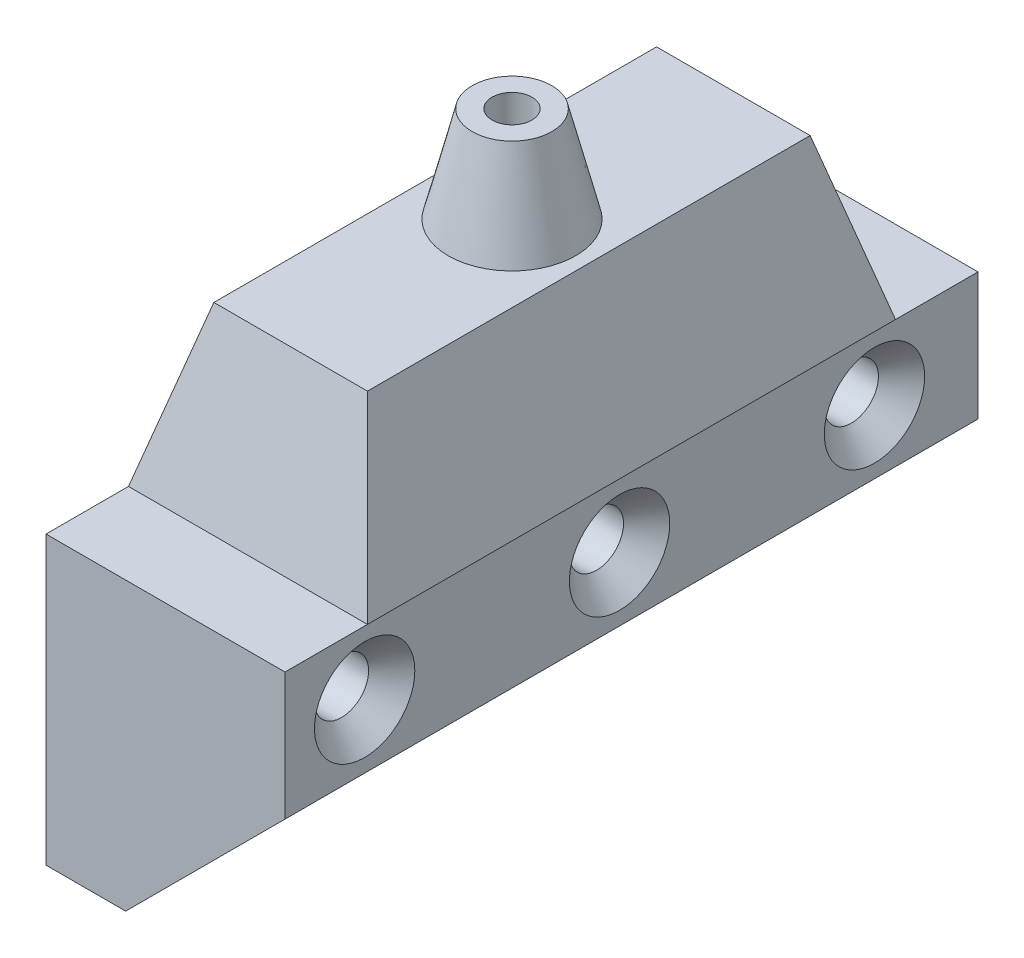
SolidWorks part; units mm, degrees
ref_plane "Plan de face" through (0, 0, 0) normal (0, 0, 1) x (1, 0, 0)
ref_plane "Plan de dessus" through (0, 0, 0) normal (0, 1, 0) x (1, 0, 0)
ref_plane "Plan de droite" through (0, 0, 0) normal (1, 0, 0) x (0, 0, -1)
sketch "Main-Sketch" plane through (0, 0, 0) normal (0, 0, 1) x (1, 0, 0)
  line L0 (0, 8) -> (2.6795, 18)
  line L1 (0, 0) -> (15, 0)
  line L2 (0, 0) -> (0, 8)
  line L3 (2.6795, 18) -> (12.3205, 18)
  line L4 (15, 0) -> (15, 8)
  line L5 (12.3205, 18) -> (15, 8)
  dimension "D1" = 15
  dimension "D2" = 8
  dimension "D3" = 165
  dimension "D4" = 10
extrude "Main-Extrusion" add sketch "Main-Sketch" along normal blind 43.5
ref_plane "Plan-Left" through (0, 11.4109, 42.5861) normal (0, 0.2588, 0.9659) x (-1, 0, 0)
ref_plane "Plan-Left2" through (0, 10.1168, 37.7564) normal (0, 0.2588, 0.9659) x (-1, 0, 0)
ref_axis "Axe-Left" through (2.6795, 18, 35.6441) along (1, 0, 0)
sketch "Left-Sketch" plane through (0, 10.1168, 37.7564) normal (0, 0.2588, 0.9659) x (-1, 0, 0)
  line L1 (0, 2.1915) -> (-15, 2.1915)
  line L2 (0, 2.1915) -> (0, -8.1613)
  line L3 (0, -8.1613) -> (-15, -8.1613)
  line L4 (-15, 2.1915) -> (-15, -8.1613)
  line L8 (0, 3.5312) -> (0, -7.7274) construction
  line L11 (-2.6795, -8.1613) -> (-12.3205, -8.1613) construction
  point P5 (0, 0)
  point P7 (0, 0)
  point P10 (-15, -11.5247)
  point P11 (0, 0)
  point P14 (-15, 3.0646)
  point P15 (-15, 0.4513)
extrude "Left-Hole" cut sketch "Left-Sketch" along normal through all
sketch "Esquisse8" plane through (15, 0, 0) normal (1, 0, 0) x (0, 0, -1)
  line L1 (-43.5, 8) -> (-38.3236, 8)
  line L2 (-43.5, 8) -> (-43.5, 13)
  line L3 (-43.5, 13) -> (-38.3236, 13)
  line L4 (-38.3236, 8) -> (-38.3236, 13)
  point P5 (-38.3236, 8)
  point P7 (-43.5, 9.3209)
  point P8 (-43.5, 10.368)
  dimension "D1" = 5
extrude "Left-Hole2" cut sketch "Esquisse8" against normal through all
ref_plane "Plan-Right" through (0, 0.5359, -2) normal (0, 0.2588, -0.9659) x (-1, 0, 0)
ref_plane "Plan-Right2" through (0, -0.7582, 2.8296) normal (0, 0.2588, -0.9659) x (-1, 0, 0)
ref_axis "Axe-Right" through (12.3205, 18, 7.8559) along (-1, 0, 0)
sketch "Right-Sketch" plane through (0, -0.7582, 2.8296) normal (0, 0.2588, -0.9659) x (-1, 0, 0)
  line L1 (-15, 9.0672) -> (0, 9.0672)
  line L2 (-15, 9.0672) -> (-15, 19.4199)
  line L3 (-15, 19.4199) -> (0, 19.4199)
  line L4 (0, 9.0672) -> (0, 19.4199)
  line L11 (-12.3205, 19.4199) -> (-2.6795, 19.4199) construction
  point P5 (-3.2068, 18.0802)
  point P7 (0, 0)
  point P10 (0, 0)
  point P12 (0, 0)
extrude "Right-Hole" cut sketch "Right-Sketch" along normal through all
sketch "Right2-Sketch" plane through (0, 0, 0) normal (-1, 0, 0) x (0, 0, 1)
  line L1 (0, 8) -> (5.1764, 8)
  line L2 (0, 8) -> (0, 13)
  line L3 (0, 13) -> (5.1764, 13)
  line L4 (5.1764, 8) -> (5.1764, 13)
  point P5 (0, 0)
  dimension "D1" = 5
extrude "Right-Hole2" cut sketch "Right2-Sketch" against normal through all
sketch "Bottom-Sketch" plane through (0, 0, 0) normal (0, 0, 1) x (1, 0, 0)
  line L0 (0, -10) -> (5, -10)
  line L1 (0, 0) -> (15, 0)
  line L2 (0, 0) -> (0, -10)
  line L3 (5, -10) -> (15, 0)
  line L4 (15, 0) -> (15, 8) construction
  dimension "D1" = 135
  dimension "D2" = 5
extrude "Bottom-Hole" add sketch "Bottom-Sketch" along normal up to surface (43.5 mm away) up to face at (7.5, 4, 43.5)
hole_wizard "Fraisage pour vis à tête fraisée M31" positions "Esquisse7" profile "Esquisse6" countersink size "M3" standard "Ansi Metric" end condition through all
sketch "Esquisse7" plane through (15, 0, 0) normal (1, 0, 0) x (0, 0, -1)
  line L0 (-43.5, 0) -> (-43.5, 8) construction
  point P0 (-38.5, 4)
  point P13 (-43.5, 4)
  dimension "D1" = 5
sketch "Esquisse6" plane through (15, 4, 38.5) normal (0, 1, 0) x (0, 0, -1)
  line L0 (0, 0) -> (0, 15)
  line L1 (0, 15) -> (1.7, 15)
  line L2 (1.7, 15) -> (1.7, 1.45)
  line L3 (1.7, 1.45) -> (3.15, 0)
  line L5 (3.15, 0) -> (0, 0)
  line L6 (-1.7, 1.45) -> (-3.15, 0) construction
  line L11 (0, -6.35) -> (0, 107.95) construction
  dimension "Diamètre du perçage jusqu'au prochain" = 3.4
  dimension "Profondeur du perçage jusqu'au prochain" = 15
  dimension "Diamètre du fraisage entrant" = 6.3
  dimension "Angle du fraisage entrant" = 90
pattern_linear "Hole-Linear-Repeat" count 3 spacing 16 along (0, 0, -1) of "Fraisage pour vis à tête fraisée M31"
ref_plane "MiddlePlan" through (0, 0, 21.75) normal (0, 0, 1) x (1, 0, 0)
ref_plane "MiddlePlan2" through (7.5, 0, 0) normal (1, 0, 0) x (0, 0, -1)
ref_axis "Middle-Axe" through (7.5, 31.2194, 21.75) along (0, -1, 0)
sketch "Screw-Sketch" plane through (0, 0, 21.75) normal (0, 0, 1) x (1, 0, 0)
  line L0 (5, 24) -> (3.5, 18)
  line L1 (3.5, 18) -> (7.5, 18)
  line L2 (7.5, 18) -> (7.5, 24)
  line L3 (7.5, 24) -> (5, 24)
  line L4 (7.5, 31.2194) -> (7.5, -0.4) construction
  line L5 (2.6795, 18) -> (12.3205, 18) construction
  point P6 (7.5, 16.8334)
  point P7 (4.5, 16.8334)
  dimension "D1" = 4
  dimension "D2" = 2.5
  dimension "D3" = 6
revolve "Screw-Revolution" add sketch "Screw-Sketch" angle 360 about axis through (7.5, 31.2194, 21.75) along (0, -1, 0)
sketch "ScrewHole-Sketch" plane through (0, 24, 0) normal (0, 1, 0) x (1, 0, 0)
  circle A0 centre (7.5, -21.75) radius 1.25
  point P2 (7.6771, -21.1023)
  dimension "D1" = 2.5
extrude "ScrewHole*" cut sketch "ScrewHole-Sketch" against normal up to surface (6 mm away) up to face at (7.5, 18, 25.75)
